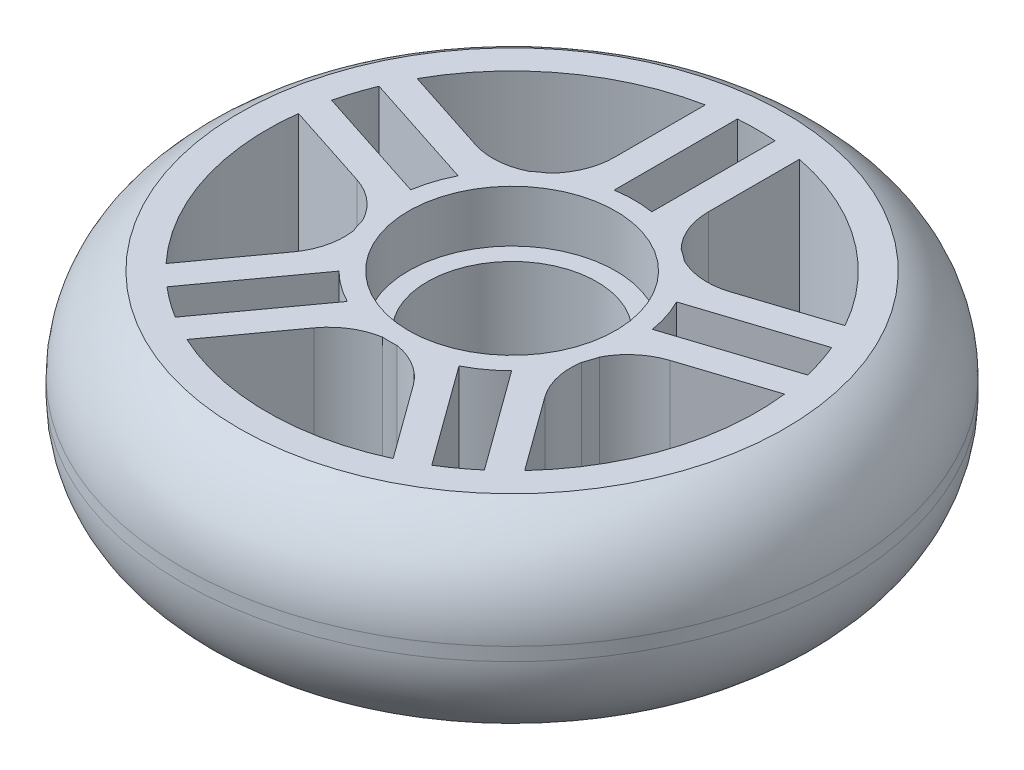
SolidWorks part; units mm, degrees
ref_plane "Front Plane" through (0, 0, 0) normal (0, 0, 1) x (1, 0, 0)
ref_plane "Top Plane" through (0, 0, 0) normal (0, 1, 0) x (1, 0, 0)
ref_plane "Right Plane" through (0, 0, 0) normal (1, 0, 0) x (0, 0, -1)
sketch "Sketch1" plane through (0, 0, 0) normal (0, 1, 0) x (1, 0, 0)
  line L0 (0, 13) -> (0, 26) construction
  line L1 (-2, 25.923) -> (-2, 12.8452)
  line L2 (5, 25.5147) -> (5, 15.8534)
  line L3 (-5, 25.5147) -> (-5, 15.8534)
  line L4 (2, 25.923) -> (2, 12.8452)
  line L5 (22.7208, 12.6398) -> (13.5324, 9.6543)
  line L6 (24.0362, 9.9127) -> (11.5985, 5.8715)
  line L7 (25.2722, 6.1085) -> (12.8346, 2.0673)
  line L8 (25.811, 3.1292) -> (16.6226, 0.1437)
  line L9 (19.0423, -17.7029) -> (13.3635, -9.8868)
  line L10 (16.8552, -19.7965) -> (9.1683, -9.2164)
  line L11 (13.6191, -22.1477) -> (5.9322, -11.5676)
  line L12 (10.9521, -23.5808) -> (5.2733, -15.7646)
  line L13 (-10.9521, -23.5808) -> (-5.2733, -15.7646)
  line L14 (-13.6191, -22.1477) -> (-5.9322, -11.5676)
  line L15 (-16.8552, -19.7965) -> (-9.1683, -9.2164)
  line L16 (-19.0423, -17.7029) -> (-13.3635, -9.8868)
  line L17 (-25.811, 3.1292) -> (-16.6226, 0.1437)
  line L18 (-25.2722, 6.1085) -> (-12.8346, 2.0673)
  line L19 (-24.0362, 9.9127) -> (-11.5985, 5.8715)
  line L20 (-22.7208, 12.6398) -> (-13.5324, 9.6543)
  circle A0 centre (0, 0) radius 9
  circle A1 centre (0, 0) radius 11
  circle A2 centre (0, 0) radius 13
  circle A3 centre (0, 0) radius 26
  circle A4 centre (0, 0) radius 35
  arc A5 (-5, 15.8534) -> (-7, 10.9545) centre (-12, 15.8534) cw
  arc A6 (5, 15.8534) -> (7, 10.9545) centre (12, 15.8534) ccw
  arc A7 (13.5324, 9.6543) -> (8.2552, 10.0425) centre (11.3693, 16.3117) cw
  arc A8 (16.6226, 0.1437) -> (12.5814, -3.2723) centre (18.7857, -6.5137) ccw
  arc A9 (13.3635, -9.8868) -> (12.102, -4.7478) centre (19.0266, -5.7723) cw
  arc A10 (5.2733, -15.7646) -> (0.7757, -12.9768) centre (-0.3898, -19.8791) ccw
  arc A11 (-5.2733, -15.7646) -> (-0.7757, -12.9768) centre (0.3898, -19.8791) cw
  arc A12 (-13.3635, -9.8868) -> (-12.102, -4.7478) centre (-19.0266, -5.7723) ccw
  arc A13 (-16.6226, 0.1437) -> (-12.5814, -3.2723) centre (-18.7857, -6.5137) cw
  arc A14 (-13.5324, 9.6543) -> (-8.2552, 10.0425) centre (-11.3693, 16.3117) ccw
  circle A15 centre (0, 0) radius 29
  point P72 (-0.0774, 0.0668)
  point P73 (0, 0)
  dimension "D1" = 70
  dimension "D2" = 18
  dimension "D3" = 22
  dimension "D4" = 26
  dimension "D5" = 52
  dimension "D6" = 2
  dimension "D8" = 7
  dimension "D11" = 58
  dimension "D7" = 3
  dimension "D9" = 7
  dimension "D10" = 5
extrude "Boss-Extrude5" add sketch "Sketch1" along normal blind 10.5 and the other way blind 10.5 contours A4 A15 region at (-34.0101, 0, 0)
fillet "Fillet3" radius 11 2 edges at (0, -10.5, 35) (0, 10.5, 35)
extrude "Boss-Extrude6" add sketch "Sketch1<8>" along normal blind 10.5 and the other way blind 10.5 contours A15 A3 | A6 L2 A3 L4 A2 | L3 A5 A2 L1 A3 | A2 A1 | A14 L20 A3 L19 A2 | L17 A13 A2 L18 A3 | A12 L16 A3 L15 A2 | L13 A11 A2 L14 A3 | A10 L12 A3 L11 A2 | L9 A9 A2 L10 A3 | A8 L8 A3 L7 A2 | L5 A7 A2 L6 A3 region at (-3.6014, 0, -18.8152) region at (0, 0, -12.6323) region at (3.6014, 0, -18.8152) region at (-16.7814, 0, -9.2394) region at (16.7814, 0, -9.2394) region at (-19.0072, 0, -2.389) region at (19.0072, 0, -2.389) region at (-13.9729, 0, 13.1049) region at (13.9729, 0, 13.1049) region at (-8.1457, 0, 17.3387) region at (8.1457, 0, 17.3387) region at (-28.1798, 0, 0)
sketch "Sketch1<8>" plane through (0, 0, 0) normal (0, 1, 0) x (1, 0, 0) same geometry as "Sketch1"
extrude "Boss-Extrude7" add sketch "Sketch1<9>" along normal blind 5 and the other way blind 5 contours A1 A0 region at (-10.6889, 0, 0)
sketch "Sketch1<9>" plane through (0, 0, 0) normal (0, 1, 0) x (1, 0, 0) same geometry as "Sketch1"
